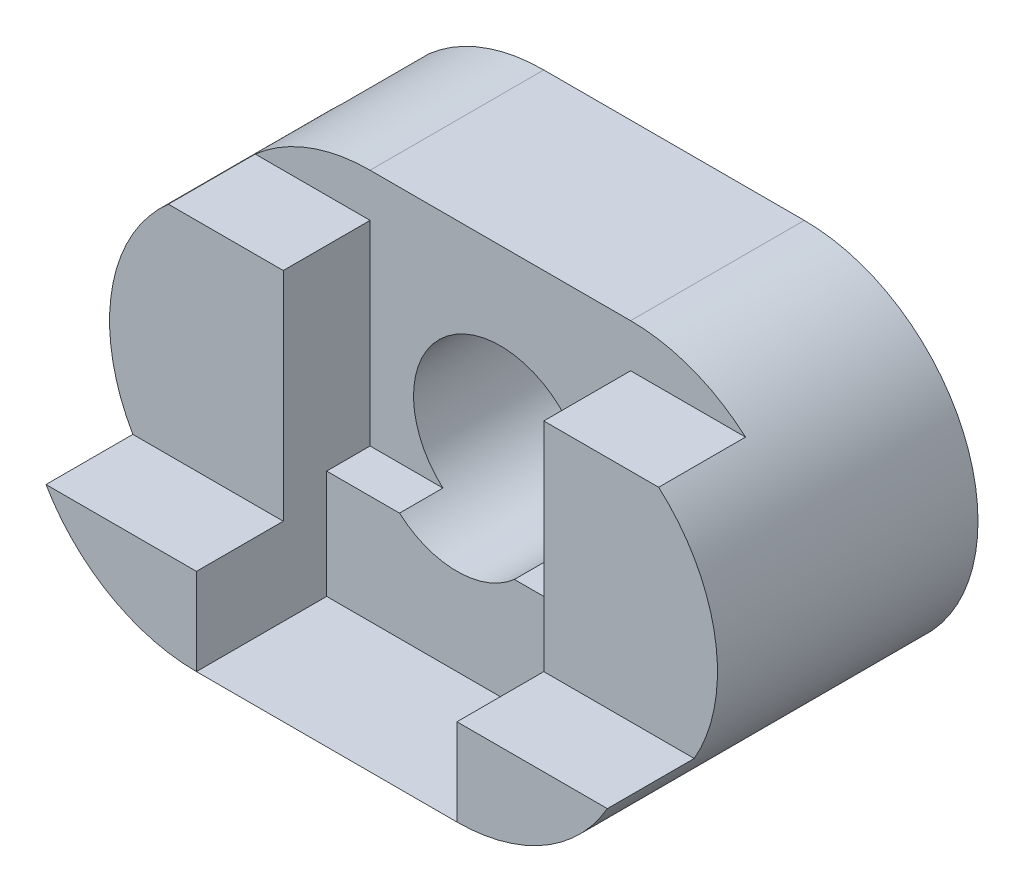
SolidWorks part; units mm, degrees
ref_plane "Front Plane" through (0, 0, 0) normal (0, 0, 1) x (1, 0, 0)
ref_plane "Top Plane" through (0, 0, 0) normal (0, 1, 0) x (1, 0, 0)
ref_plane "Right Plane" through (0, 0, 0) normal (1, 0, 0) x (0, 0, -1)
sketch "Sketch1" plane through (0, 0, 0) normal (0, 0, 1) x (1, 0, 0)
  line L0 (0, 0) -> (60, 0) construction
  line L1 (0, 40) -> (60, 40)
  line L2 (0, -40) -> (60, -40)
  arc A0 (0, 40) -> (0, -40) centre (0, 0) ccw
  arc A1 (60, -40) -> (60, 40) centre (60, 0) ccw
  point P3 (30, 0)
  dimension "D2" = 60
  dimension "D1" = 80
extrude "Boss-Extrude1" add sketch "Sketch1" along normal blind 80
sketch "Sketch2" plane through (0, 0, 80) normal (0, 0, 1) x (1, 0, 0)
  line L0 (60, 40) -> (0, 40) construction
  circle A0 centre (30, 0) radius 20
  arc A1 (0, 40) -> (0, -40) centre (0, 0) ccw construction
  arc A2 (60, -40) -> (60, 40) centre (60, 0) ccw construction
  point P2 (30, 40)
  point P5 (-40, 0)
  point P9 (100, 0)
  dimension "D1" = 40
  dimension "D2" = 40
  dimension "D3" = 70
extrude "Cut-Extrude1" cut sketch "Sketch2" against normal blind 80
sketch "Sketch4" plane through (0, 0, 0) normal (1, 0, 0) x (0, 0, -1)
  line L0 (-80, -40) -> (0, -40) construction
  line L1 (-80, 40) -> (-60, 40)
  line L2 (-80, 40) -> (-80, -20)
  line L3 (-80, -20) -> (-60, -20)
  line L4 (-60, 40) -> (-60, -20)
  dimension "D1" = 20
  dimension "D2" = 20
extrude "Cut-Extrude3" cut sketch "Sketch4" along normal blind 170 and the other way blind 60
sketch "Sketch5" plane through (0, 0, 0) normal (1, 0, 0) x (0, 0, -1)
  line L1 (-60, 40) -> (-40, 40)
  line L2 (-60, 40) -> (-60, 30)
  line L3 (-60, 30) -> (-40, 30)
  line L4 (-40, 40) -> (-40, 30)
  dimension "D1" = 20
  dimension "D2" = 10
extrude "Cut-Extrude4" cut sketch "Sketch5" against normal blind 170 and the other way blind 170
sketch "Sketch6" plane through (0, 0, 80) normal (0, 0, 1) x (1, 0, 0)
  line L0 (0, -40) -> (60, -40) construction
  line L1 (60, -40) -> (0, -40)
  line L2 (60, -40) -> (60, -15)
  line L3 (60, -15) -> (0, -15)
  line L4 (0, -40) -> (0, -15)
  line L5 (-26.4575, 30) -> (86.4575, 30) construction
  arc A0 (0, 40) -> (0, -40) centre (0, 0) ccw construction
  arc A1 (94.641, -20) -> (86.4575, 30) centre (60, 0) ccw construction
  arc A2 (-26.4575, 30) -> (-34.641, -20) centre (0, 0) ccw construction
  point P6 (-40, 0)
  point P10 (99.4748, 6.4608)
  point P15 (-39.4748, 6.4608)
  point P19 (99.4748, 6.4608)
  dimension "D1" = 60
  dimension "D2" = 25
extrude "Cut-Extrude5" cut sketch "Sketch6" against normal blind 30
sketch "Sketch7" plane through (0, -15, 0) normal (0, -1, 0) x (1, 0, 0)
  line L1 (16.7712, 60) -> (0, 60)
  line L2 (16.7712, 60) -> (16.7712, 50)
  line L3 (16.7712, 50) -> (0, 50)
  line L4 (0, 60) -> (0, 50)
  line L5 (43.2288, 60) -> (60, 60)
  line L6 (43.2288, 60) -> (43.2288, 50)
  line L7 (43.2288, 50) -> (60, 50)
  line L8 (60, 60) -> (60, 50)
  line L9 (60, 60) -> (0, 60)
  line L10 (60, 60) -> (60, 50)
  line L11 (60, 50) -> (0, 50)
  line L12 (0, 60) -> (0, 50)
  line M1 (0, 60) -> (0, 50)
  line M2 (0, 50) -> (16.7712, 50)
  line M3 (16.7712, 50) -> (16.7712, 60)
  line M4 (16.7712, 60) -> (0, 60)
extrude "Cut-Extrude6" cut sketch "Sketch7" against normal blind 62 contours L11 L6 L9 M3 | L8 L5 L6 L7 | M4 M1 M2 M3 region at (8.3856, -15, 55) region at (30, -15, 55) region at (51.6144, -15, 55)
sketch "Sketch8" plane through (0, 0, 50) normal (0, 0, 1) x (1, 0, 0)
  line L0 (60, -40) -> (60, 30) construction
  line L1 (0, -40) -> (60, -40)
  line L2 (0, -40) -> (0, -15)
  line L3 (0, -15) -> (60, -15)
  line L4 (60, -40) -> (60, -15)
  dimension "D1" = 25
extrude "Boss-Extrude2" add sketch "Sketch8" along normal blind 30
sketch "Sketch9" plane through (0, 0, 50) normal (0, 0, -1) x (-1, 0, 0)
  line L0 (-43.2288, -15) -> (-16.7712, -15)
  arc A0 (-43.2288, -15) -> (-16.7712, -15) centre (-30, 0) ccw
  arc A1 (-43.2288, -15) -> (-16.7712, -15) centre (-30, 0) ccw construction
extrude "Cut-Extrude7" cut sketch "Sketch9" against normal blind 30
sketch "Sketch10" plane through (0, 0, 80) normal (0, 0, 1) x (1, 0, 0)
  line L0 (60, -20) -> (60, -40)
  line L1 (60, -20) -> (94.641, -20)
  arc A0 (94.641, -20) -> (60, -40) centre (60, 0) cw
  arc A1 (60, -40) -> (94.641, -20) centre (60, 0) ccw construction
extrude "Cut-Extrude8" cut sketch "Sketch10" against normal blind 30
sketch "Sketch11" plane through (0, 0, 50) normal (0, 0, 1) x (1, 0, 0)
  line L0 (0, 30) -> (60, 30)
  line L1 (60, 30) -> (60, -15)
  line L2 (60, -15) -> (43.2288, -15)
  line L3 (16.7712, -15) -> (0, -15)
  line L4 (0, -15) -> (0, 30)
  arc A0 (43.2288, -15) -> (16.7712, -15) centre (30, 0) ccw
  arc A1 (43.2288, -15) -> (16.7712, -15) centre (30, 0) ccw construction
  line M1 (0, 30) -> (0, -15)
  line M2 (0, -15) -> (16.7712, -15)
  arc M3 (16.7712, -15) -> (43.2288, -15) centre (30, 0) cw
  line M4 (43.2288, -15) -> (60, -15)
  line M5 (60, -15) -> (60, 30)
  line M6 (60, 30) -> (0, 30)
extrude "Cut-Extrude9" cut sketch "Sketch11" against normal blind 10 contours M6 M1 M2 M3 M4 M5 region at (30, 29.25, 50)
sketch "Sketch12" plane through (0, 0, 50) normal (0, 0, 1) x (1, 0, 0)
  line L0 (60, -20) -> (94.641, -20)
  line L1 (60, -20) -> (60, -40)
  arc A0 (94.641, -20) -> (60, -40) centre (60, 0) cw
  arc A1 (60, -40) -> (94.641, -20) centre (60, 0) ccw construction
  dimension "D1" = 40
extrude "Boss-Extrude3" add sketch "Sketch12" along normal blind 10
sketch "Sketch17" plane through (0, 0, 60) normal (0, 0, 1) x (1, 0, 0)
  line L0 (60, -15) -> (97.081, -15)
  line L1 (60, -15) -> (60, -40)
  line L2 (60, 30) -> (60, -15) construction
  arc A0 (60, -40) -> (86.4575, 30) centre (60, 0) ccw construction
  arc A1 (97.081, -15) -> (60, -40) centre (60, 0) cw
  line M3 (60, -15) -> (60, -40)
  arc M4 (60, -40) -> (86.4575, 30) centre (60, 0) ccw
extrude "Boss-Extrude4" add sketch "Sketch17" along normal blind 20 contours L0 M3 M4 region at (74.7476, -25.3281, 60)
sketch "Sketch18" plane through (0, 0, 80) normal (0, 0, 1) x (1, 0, 0)
  line L1 (59.8859, -20) -> (97.081, -20)
  line L2 (59.8859, -20) -> (59.8859, -15)
  line L3 (59.8859, -15) -> (97.081, -15)
  line L4 (97.081, -20) -> (97.081, -15)
  dimension "D1" = 37.1951
extrude "Cut-Extrude23" cut sketch "Sketch18" against normal blind 20
sketch "Sketch19" plane through (0, 0, 80) normal (0, 0, 1) x (1, 0, 0)
  line L0 (0, -15) -> (0, -40)
  line L1 (0, -15) -> (16.7712, -15)
  line L2 (43.2288, -15) -> (59.8859, -15)
  line L3 (59.8859, -15) -> (60, -40)
  line L4 (0, -40) -> (60, -40) construction
  line L5 (60, -40) -> (0, -40)
  arc A0 (60, -40) -> (94.641, -20) centre (60, 0) ccw construction
  arc A1 (16.7712, -15) -> (43.2288, -15) centre (30, 0) ccw
  line M1 (59.8859, -20) -> (59.8859, -15)
  line M2 (59.8859, -15) -> (43.2288, -15)
  arc M3 (43.2288, -15) -> (16.7712, -15) centre (30, 0) cw
  line M4 (16.7712, -15) -> (0, -15)
  line M5 (0, -15) -> (0, -20)
  line M8 (0, -40) -> (60, -40)
  line M10 (94.641, -20) -> (59.8859, -20)
extrude "Cut-Extrude25" cut sketch "Sketch19" against normal blind 30 contours L3 L0 M10 M1 M2 M3 M4 M5 M8 region at (29.9684, -28.1793, 80)
sketch "Sketch21" plane through (59.8162, 0.273, 0) normal (-1, -0.0046, 0) x (0, 0, 1)
  line L1 (80, -40.2734) -> (50, -40.2734)
  line L2 (80, -40.2734) -> (80, -15.2731)
  line L3 (80, -15.2731) -> (50, -15.2731)
  line L4 (50, -40.2734) -> (50, -15.2731)
extrude "Cut-Extrude31" cut sketch "Sketch21" along normal blind 30
ref_plane "Plane1" through (0, 0, 50) normal (0, 0, 1) x (1, 0, 0)
sketch "Sketch24" plane through (0, 0, 50) normal (0, 0, 1) x (1, 0, 0)
  line L0 (59.8859, -15) -> (97.081, -15)
  line L1 (59.8859, -15) -> (59.8859, 30.0007)
  line L2 (59.8859, 30.0007) -> (86.4568, 30.0007)
  arc A0 (86.4568, 30.0007) -> (97.081, -15) centre (60, 0) cw
  arc A1 (60, -40) -> (60, 40) centre (60, 0) ccw construction
  dimension "D1" = 10
extrude "Cut-Extrude32" cut sketch "Sketch24" along normal blind 30
sketch "Sketch26" plane through (59.8162, 0.273, 0) normal (-1, -0.0046, 0) x (0, 0, 1)
  line L1 (50, -15.2731) -> (60, -15.2731)
  line L2 (50, -15.2731) -> (50, -20.2732)
  line L3 (50, -20.2732) -> (60, -20.2732)
  line L4 (60, -15.2731) -> (60, -20.2732)
extrude "Cut-Extrude33" cut sketch "Sketch26" against normal blind 57
sketch "Sketch29" plane through (0, -20, 0) normal (0, 1, 0) x (1, 0, 0)
  line L1 (59.9087, -50) -> (94.641, -50)
  line L2 (59.9087, -50) -> (59.9087, -80)
  line L3 (59.9087, -80) -> (94.641, -80)
  line L4 (94.641, -50) -> (94.641, -80)
extrude "Cut-Extrude37" cut sketch "Sketch29" against normal blind 57
sketch "Sketch30" plane through (0, -20, 0) normal (0, -1, 0) x (1, 0, 0)
  line L1 (59.9087, 60) -> (94.641, 60)
  line L2 (59.9087, 60) -> (59.9087, 50)
  line L3 (59.9087, 50) -> (94.641, 50)
  line L4 (94.641, 60) -> (94.641, 50)
extrude "Cut-Extrude38" cut sketch "Sketch30" against normal blind 57
sketch "Sketch31" plane through (94.641, 0, 0) normal (-1, 0, 0) x (0, 0, 1)
  line L1 (50, -19.8415) -> (60, -19.8415)
  line L2 (50, -19.8415) -> (50, -20)
  line L3 (50, -20) -> (60, -20)
  line L4 (60, -19.8415) -> (60, -20)
extrude "Cut-Extrude39" cut sketch "Sketch31" against normal blind 57
sketch "Sketch32" plane through (0.0925, -20.273, 0) normal (-0.0046, 1, 0) x (1, 0.0046, 0)
  line L1 (94.6408, -50) -> (94.5495, -50)
  line L2 (94.6408, -50) -> (94.6408, -60)
  line L3 (94.6408, -60) -> (94.5495, -60)
  line L4 (94.5495, -50) -> (94.5495, -60)
extrude "Cut-Extrude40" cut sketch "Sketch32" against normal blind 57
sketch "Sketch33" plane through (0, 0, 50) normal (0, 0, 1) x (1, 0, 0)
  line L0 (60, -20) -> (60, -40)
  line L1 (60, -20) -> (94.641, -20)
  line L3 (0, -40) -> (60, -40) construction
  arc A0 (60, -40) -> (86.4575, 30) centre (60, 0) ccw construction
  arc A1 (60, -40) -> (94.641, -20) centre (60, 0) ccw
  dimension "D1" = 5
extrude "Boss-Extrude6" add sketch "Sketch33" along normal blind 30
sketch "Sketch34" plane through (0, 0, 50) normal (0, 0, 1) x (1, 0, 0)
  line L0 (60, 30) -> (60, -20)
  line L1 (60, -20) -> (94.641, -20)
  line L2 (60, 30) -> (86.4575, 30)
  arc A0 (86.4575, 30) -> (94.641, -20) centre (60, 0) cw
  arc A1 (94.641, -20) -> (86.4575, 30) centre (60, 0) ccw construction
extrude "Boss-Extrude7" add sketch "Sketch34" along normal blind 10
ref_plane "Plane2" through (0, 30, 0) normal (0, 1, 0) x (1, 0, 0)
sketch "Sketch37" plane through (0, 0, 0) normal (1, 0, 0) x (0, 0, -1)
  line L0 (-40, 40) -> (0, 40) construction
  line L1 (0, -40) -> (-20, -40)
  line L2 (0, -40) -> (0, 30)
  line L3 (0, 30) -> (-20, 30)
  line L4 (-20, -40) -> (-20, 30)
  dimension "D1" = 20
  dimension "D2" = 10
extrude "Cut-Extrude47" cut sketch "Sketch37" against normal blind 68
sketch "Sketch45" plane through (0, -40, 0) normal (0, -1, 0) x (-1, 0, 0)
  line L1 (-60, -50) -> (0, -50)
  line L2 (-60, -50) -> (-60, -80)
  line L3 (-60, -80) -> (0, -80)
  line L4 (0, -50) -> (0, -80)
extrude "Boss-Extrude10" add sketch "Sketch45" against normal blind 0.0001
sketch "Sketch46" plane through (0, 0, 20) normal (0, 0, -1) x (-1, 0, 0)
  line L0 (0, 30) -> (0, -40) construction
  line L1 (26.4575, 30) -> (0, 30)
  line L2 (0, 30) -> (0, -40)
  arc A0 (26.4575, 30) -> (0, -40) centre (0, 0) cw
extrude "Boss-Extrude11" add sketch "Sketch46" along normal blind 20
ref_plane "Plane5" through (0, 30, 0) normal (0, 1, 0) x (1, 0, 0)
sketch "Sketch49" plane through (0, 0, 0) normal (1, 0, 0) x (0, 0, -1)
  line L0 (-40, 40) -> (0, 40) construction
  line L1 (0, -40) -> (-20, -40)
  line L2 (0, -40) -> (0, 30)
  line L3 (0, 30) -> (-20, 30)
  line L4 (-20, -40) -> (-20, 30)
  dimension "D1" = 20
  dimension "D2" = 10
extrude "Cut-Extrude54" cut sketch "Sketch49" against normal blind 95
